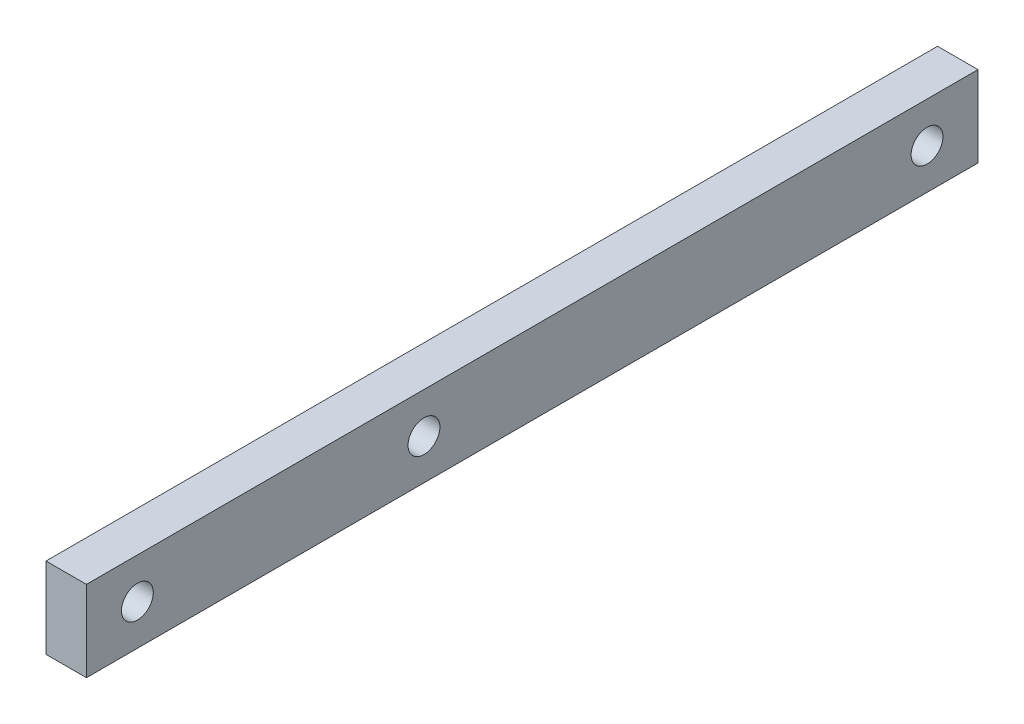
SolidWorks part; units mm, degrees
ref_plane "Front Plane" through (0, 0, 0) normal (0, 0, 1) x (1, 0, 0)
ref_plane "Top Plane" through (0, 0, 0) normal (0, 1, 0) x (1, 0, 0)
ref_plane "Right Plane" through (0, 0, 0) normal (1, 0, 0) x (0, 0, -1)
sketch "Sketch2" plane through (0, 0, 0) normal (0, 0, 1) x (1, 0, 0)
  line L1 (-3.175, -6.35) -> (3.175, -6.35)
  line L2 (-3.175, -6.35) -> (-3.175, 6.35)
  line L3 (-3.175, 6.35) -> (3.175, 6.35)
  line L4 (3.175, -6.35) -> (3.175, 6.35)
  line L5 (-3.175, -6.35) -> (3.175, 6.35) construction
  line L6 (-3.175, 6.35) -> (3.175, -6.35) construction
  point P0 (0, 0)
  dimension "D1" = 6.35
  dimension "D2" = 12.7
extrude "Boss-Extrude1" add sketch "Sketch2" along normal blind 70 and the other way blind 70
sketch "Sketch4" plane through (3.175, 0, 0) normal (1, 0, 0) x (0, 0, -1)
  line L0 (0, 0) -> (0, -6.35) construction
  line L1 (70, -6.35) -> (-70, -6.35) construction
  line L2 (-70, -6.35) -> (-70, 6.35) construction
  line L3 (-62, 0) -> (-17, 0) construction
  circle A0 centre (-62, 0) radius 2.5
  circle A1 centre (62, 0) radius 2.5
  circle A2 centre (-17, 0) radius 2.5
  dimension "D1" = 5
  dimension "D2" = 8
  dimension "D3" = 45
extrude "Cut-Extrude1" cut sketch "Sketch4" against normal through all
